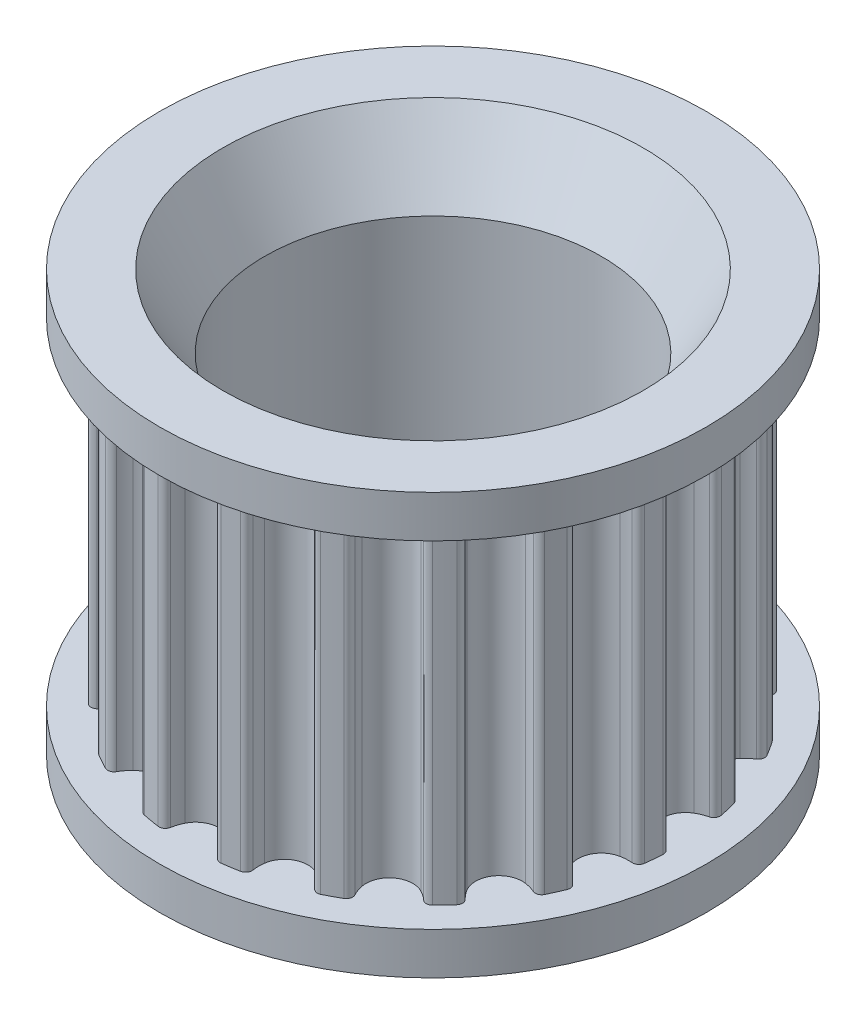
SolidWorks part; units mm, degrees
ref_plane "Front Plane" through (0, 0, 0) normal (0, 0, 1) x (1, 0, 0)
ref_plane "Top Plane" through (0, 0, 0) normal (0, 1, 0) x (1, 0, 0)
ref_plane "Right Plane" through (0, 0, 0) normal (1, 0, 0) x (0, 0, -1)
sketch "Sketch1" plane through (0, 0, 0) normal (0, 1, 0) x (1, 0, 0)
  circle A0 centre (0, 0) radius 6.5
  circle A1 centre (0, 0) radius 4
  dimension "D1" = 13
  dimension "D2" = 8
extrude "Boss-Extrude1" add sketch "Sketch1" along normal blind 10
ref_plane "Plane1" through (0, 1, 0) normal (0, 1, 0) x (1, 0, 0)
sketch "Sketch2" plane through (0, 1, 0) normal (0, 1, 0) x (1, 0, 0)
  line L0 (0, 0) -> (0, 8.965) construction
  line L1 (-0.0005, -0.003) -> (0.9645, 5.5335) construction
  line L2 (-0.0002, -0.0007) -> (1.3963, 5.6666) construction
  line L3 (0, 5.795) -> (0, 6.5)
  line L4 (1.9605, 5.4533) -> (2.199, 6.1167)
  circle A0 centre (0, 0) radius 5.795 construction
  arc A1 (0, 5.795) -> (0.2458, 5.7898) centre (0, 0) cw
  arc A2 (0.2458, 5.7898) -> (0.3895, 5.6398) centre (0.2395, 5.6399) cw
  arc A3 (0.3895, 5.6398) -> (0.4279, 5.3644) centre (1.3895, 5.639) ccw
  arc A4 (0.4279, 5.3644) -> (1.4122, 5.1929) centre (0.9616, 5.5168) ccw
  circle A5 centre (0, 0) radius 5.045 construction
  arc A7 (1.5415, 5.439) -> (1.4122, 5.1929) centre (0.6002, 5.7766) cw
  arc A8 (1.7274, 5.5315) -> (1.5415, 5.439) centre (1.6827, 5.3884) ccw
  arc A9 (1.9605, 5.4533) -> (1.7274, 5.5315) centre (0, 0) ccw
  arc A11 (2.199, 6.1167) -> (0, 6.5) centre (0, 0) ccw
  circle A12 centre (0, 0) radius 6.5
  arc A13 (-1.5551, -6.3112) -> (-1.1161, -6.4035) centre (0, 0) ccw
  point P12 (0.3991, 5.5008)
  point P17 (0.995, 5.7089)
  point P18 (1.3864, 5.6267)
  dimension "D1" = 11.59
  dimension "D2" = 0.15
  dimension "D4" = 0.555
  dimension "D7" = 0.75
  dimension "D8" = 0
  dimension "D3" = 1
  dimension "D5" = 0.4
  dimension "D6" = 1
extrude "Cut-Extrude1" cut sketch "Sketch2" along normal blind 8 contours L4 A11 L3 A1 A2 A3 A4 A7 A8 A9 region at (1.0152, 1, -5.8244)
ref_axis "Axis1" through (0, 10, 0) along (0, -1, 0)
pattern_circular "CirPattern1" count 19 over 360 about axis through (0, 10, 0) along (0, -1, 0) of "Cut-Extrude1"
chamfer "Chamfer1" distance 1 angle 60 2 edges at (0, 10, 4) (0, 0, 4) first distance on face at (0, 10, 6.5) first distance on face at (0, 10, 4)
